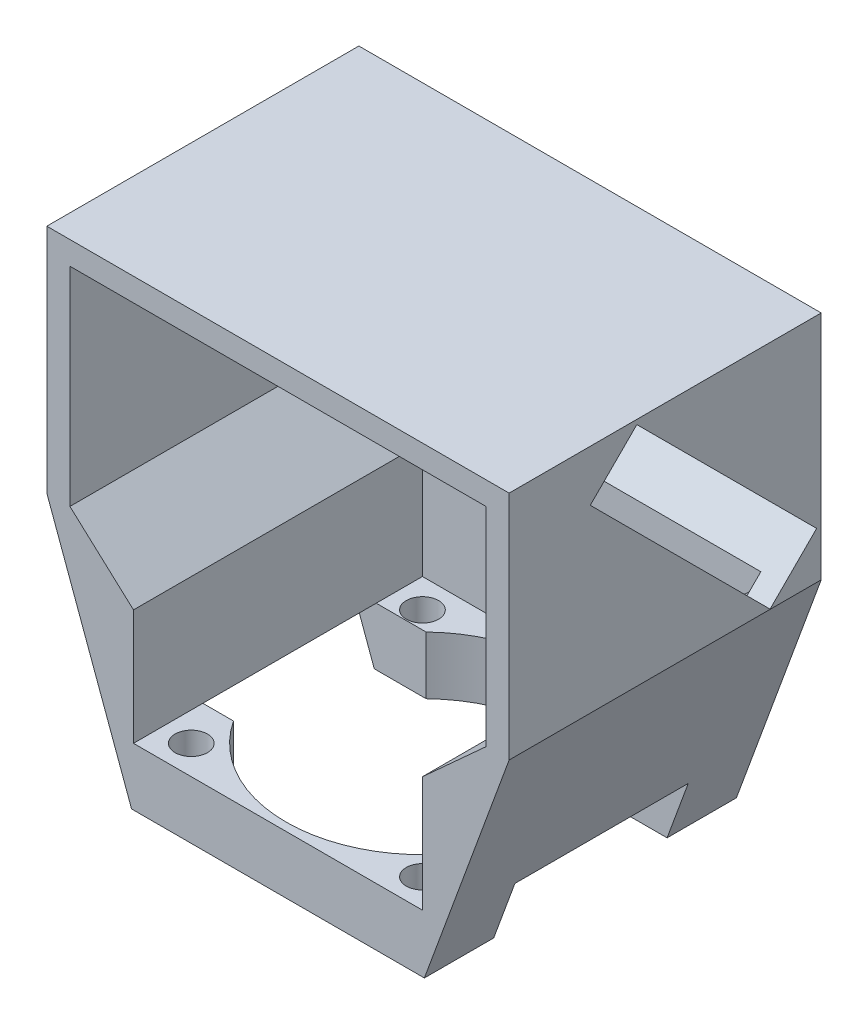
SolidWorks part; units mm, degrees
ref_plane "Front Plane" through (0, 0, 0) normal (1, 0, 0) x (0, 1, 0)
ref_plane "Top Plane" through (0, 0, 0) normal (0, 0, 1) x (0, 1, 0)
ref_plane "Right Plane" through (0, 0, 0) normal (0, 1, 0) x (-1, 0, 0)
sketch "Sketch2" plane through (0, 0, 0) normal (0, 0, 1) x (0, 1, 0)
  line L1 (-20, -20) -> (20, -20)
  line L2 (-20, -20) -> (-20, 20)
  line L3 (-20, 20) -> (20, 20)
  line L4 (20, -20) -> (20, 20)
  line L5 (-20, -20) -> (20, 20) construction
  line L6 (-20, 20) -> (20, -20) construction
  line L11 (-25, 12.5) -> (-15, -12.5) construction
  line L12 (-25, -12.5) -> (-15, 12.5) construction
  line L13 (-15, 12.5) -> (-5, 12.5)
  line L14 (-15, 12.5) -> (-15, -12.5)
  line L15 (-15, -12.5) -> (-5, -12.5)
  line L16 (-5, 12.5) -> (-5, -12.5)
  line L17 (20, 12.5) -> (5.2, 12.5)
  line L18 (20, 12.5) -> (20, -12.5)
  line L19 (20, -12.5) -> (5.2, -12.5)
  line L20 (5.2, 12.5) -> (5.2, -12.5)
  line L21 (-20, 12.5) -> (-15, 12.5)
  line L22 (-20, 12.5) -> (-20, -12.5)
  line L23 (-20, -12.5) -> (-15, -12.5)
  line L24 (-15, 12.5) -> (-15, -12.5)
  point P0 (0, 0)
  point P6 (-20, 0)
  dimension "D1" = 40
  dimension "D2" = 40
  dimension "D3" = 25
  dimension "D4" = 10
  dimension "D5" = 10
  dimension "D6" = 14.8
extrude "Boss-Extrude1" add sketch "Sketch2" along normal blind 25 contours L2 L23 L14 L21 region at (0, -17.5, 0)
extrude "Boss-Extrude2" add sketch "Sketch2<3>" against normal blind 2 contours L3 L4 L1 L2
sketch "Sketch2<3>" plane through (0, 0, 0) normal (0, 0, 1) x (0, 1, 0) same geometry as "Sketch2"
sketch "Sketch3" plane through (0, -20, 0) normal (0, -1, 0) x (1, 0, 0)
  line L1 (-12.5, 25) -> (12.5, 25)
  line L2 (-12.5, 25) -> (-12.5, 0)
  line L3 (-12.5, 0) -> (12.5, 0)
  line L4 (12.5, 25) -> (12.5, 0)
  circle A0 centre (0, 12.5) radius 11.8
  circle A1 centre (-10, 22.5) radius 1.4
  circle A2 centre (10, 22.5) radius 1.4
  circle A3 centre (10, 2.5) radius 1.4
  circle A4 centre (-10, 2.5) radius 1.4
  dimension "D1" = 4
extrude "Cut-Extrude1" cut sketch "Sketch3" against normal blind 21 and the other way through all contours A1 | A0 | A2 | A3 | A4 region at (0, -20, 12.5) region at (-10, -20, 22.5) region at (10, -20, 22.5) region at (10, -20, 2.5) region at (-10, -20, 2.5)
sketch "Sketch6" plane through (20, 0, 0) normal (1, 0, 0) x (0, 1, 0)
  line L0 (0, 0) -> (18, 18)
  line L1 (20, 0) -> (18, 0)
  line L2 (20, 0) -> (20, 25)
  line L3 (20, 25) -> (18, 25)
  line L4 (18, 0) -> (18, 25)
  line L5 (18, 0) -> (0, 0)
  line L6 (18, 0) -> (18, 18)
  line L7 (18, 18) -> (0, 18)
  line L8 (0, 0) -> (0, 18)
  dimension "D1" = 25
  dimension "D2" = 2
  dimension "D3" = 18
  dimension "D4" = 18
extrude "Boss-Extrude3" add sketch "Sketch6" against normal up to surface (40 mm away) contours L3 L4 L0 | L4 L3 L2 region at (20, 12, 6) region at (20, 19, 12.5) up to face at (-20, 0, -1)
sketch "Sketch7" plane through (0, 0, 0) normal (0, -0.7071, 0.7071) x (1, 0, 0)
  line L0 (20, 0) -> (20, 25.4558) construction
  line L1 (-20, 25.4558) -> (0, 25.4558)
  line L2 (-20, 25.4558) -> (-20, 12.7279)
  line L3 (-20, 12.7279) -> (0, 12.7279)
  line L4 (0, 25.4558) -> (0, 12.7279)
  line L5 (-18, 1.7279) -> (18, 1.7279)
  line L6 (-18, 1.7279) -> (-18, 23.7279)
  line L7 (-18, 23.7279) -> (18, 23.7279)
  line L8 (18, 1.7279) -> (18, 23.7279)
  line L9 (-18, 1.7279) -> (18, 23.7279) construction
  line L10 (-18, 23.7279) -> (18, 1.7279) construction
  line L11 (16, 4.7279) -> (20, 4.7279)
  line L12 (16, 4.7279) -> (16, 20.7279)
  line L13 (16, 20.7279) -> (20, 20.7279)
  line L14 (20, 4.7279) -> (20, 20.7279)
  line L15 (16, 4.7279) -> (20, 20.7279) construction
  line L16 (16, 20.7279) -> (20, 4.7279) construction
  point P9 (18, 12.7279)
  line M13 (20, 0) -> (20, 25.4558)
  dimension "D1" = 12.7279
  dimension "D2" = 22
  dimension "D3" = 36
  dimension "D4" = 16
extrude "Cut-Extrude2" cut sketch "Sketch7" against normal blind 4 contours L12 L13 L8 L7 L4 L3 L6 L5 L11 | L7 L6 L3 L4 | L13 L12 L11 L8 | L13 L8 L11 M13 region at (2.2028, 7.6298, 7.6298) region at (-9, 12.8891, 12.8891) region at (19, 9, 9) region at (17, 9, 9)
sketch "Sketch8" plane through (0, 0, 0) normal (0, 0, 1) x (1, 0, 0)
  line L0 (-18, 0) -> (-12.5, -15)
  line L1 (-12.5, -15) -> (-20, -15)
  line L2 (-12.5, -15) -> (-12.5, 0)
  line L3 (-12.5, 0) -> (-20, 0)
  line L4 (-20, -15) -> (-20, 0)
  line L5 (12.5, -15) -> (20, -15)
  line L6 (12.5, -15) -> (12.5, 0)
  line L7 (12.5, 0) -> (20, 0)
  line L8 (20, -15) -> (20, 0)
  line L9 (-20, 0) -> (-12.5, -20.4545)
  line L10 (-12.5, -15) -> (-12.5, -20.4545)
  line L11 (18, 0) -> (12.5, -15)
  line L12 (20, 0) -> (12.2526, -21.1292)
  line L13 (12.5, -15) -> (12.5, -20.4545)
  line M9 (20, 0) -> (-20, 0)
  line M11 (-20, -20) -> (-12.5, -20)
  line M12 (-12.5, -20) -> (-12.5, -15)
  line M14 (12.5, -15) -> (12.5, -20)
  line M15 (12.5, -20) -> (20, -20)
extrude "Boss-Extrude4" add sketch "Sketch8" along normal up to surface (25 mm away) contours L9 L1 L0 M9 | L1 L9 M11 M12 | L12 L11 L5 M9 | L12 L5 M14 M15 region at (-16.25, -7.5, 0) region at (-13.1709, -16.7949, 0) region at (16.25, -7.5, 0) region at (13.1709, -16.7949, 0) up to face at (0, -17.5, 25)
sketch "Sketch9" plane through (0, 0, 25) normal (0, 0, 1) x (1, 0, 0)
  line L1 (-20, 18) -> (-18, 18)
  line L2 (-20, 18) -> (-20, 0)
  line L3 (-20, 0) -> (-18, 0)
  line L4 (-18, 18) -> (-18, 0)
  line L5 (20, 18) -> (18, 18)
  line L6 (20, 18) -> (20, 0)
  line L7 (20, 0) -> (18, 0)
  line L8 (18, 18) -> (18, 0)
extrude "Boss-Extrude5" add sketch "Sketch9" against normal up to surface (7 mm away) up to face at (5.4286, 7.7143, 7.7143)
sketch "Sketch10" plane through (0, 0, 0) normal (0, 0, 1) x (1, 0, 0)
  line L0 (-20, 0) -> (-12.6667, -20)
  line L1 (-12.6667, -20) -> (-20, -20)
  line L2 (-20, -20) -> (-20, 0)
  line L3 (20, 0) -> (20, -20)
  line L4 (20, -20) -> (12.6667, -20)
  line L5 (12.6667, -20) -> (20, 0)
extrude "Cut-Extrude3" cut sketch "Sketch10" against normal blind 4
sketch "Sketch11" plane through (0, 0, 0) normal (0, 0, 1) x (1, 0, 0)
  line L0 (-12.5, -5) -> (-18, 0)
  line L1 (-12.5, -15) -> (12.5, -15)
  line L2 (-12.5, -15) -> (-12.5, -5)
  line L3 (-12.5, -5) -> (12.5, -5)
  line L4 (12.5, -15) -> (12.5, -5)
  line L5 (-20, 0) -> (-18, 0)
  line L6 (18, 0) -> (12.5, -5)
  line L7 (18, 0) -> (12.5, -15)
  line L8 (-18, 0) -> (-12.5, -15)
  line M6 (-18, 0) -> (-12.5, -15)
  line M8 (12.5, -15) -> (18, 0)
  dimension "D1" = 10
extrude "Boss-Extrude6" add sketch "Sketch11" along normal up to surface (25 mm away) contours L6 L4 M8 | L2 L0 M6 region at (-14.3333, -6.6667, 0) region at (14.3333, -6.6667, 0) up to face at (0, 1, 25)
sketch "Sketch12" plane through (20, 0, 0) normal (1, 0, 0) x (0, 1, 0)
  line L0 (6.1716, 0.5147) -> (17.4853, 11.8284)
  line L1 (6.1716, 0.5147) -> (1.9289, 4.7574)
  line L2 (17.4853, 11.8284) -> (13.2426, 16.0711)
  line L3 (1.9289, 4.7574) -> (13.2426, 16.0711)
  dimension "D1" = 6
extrude "Cut-Extrude4" cut sketch "Sketch12" against normal blind 4
sketch "Sketch13" plane through (18, 0, 0) normal (-1, 0, 0) x (0, -1, 0)
  line L0 (-19.6066, 13.9497) -> (-4.0503, -1.6066)
  line L1 (-19.6066, 13.9497) -> (-15.5761, 17.9803)
  line L2 (-4.0503, -1.6066) -> (-0.0197, 2.4239)
  line L3 (-15.5761, 17.9803) -> (-0.0197, 2.4239)
  dimension "D1" = 5.7
extrude "Cut-Extrude5" cut sketch "Sketch13" against normal blind 10
sketch "Sketch14" plane through (20, 0, 0) normal (1, 0, 0) x (0, 1, 0)
  line L0 (1.9289, 4.7574) -> (2.1411, 4.5452)
  line L1 (1.9289, 4.7574) -> (13.3484, 16.1769)
  line L2 (2.1411, 4.5452) -> (13.5606, 15.9647)
  line L3 (13.3484, 16.1769) -> (13.5606, 15.9647)
extrude "Boss-Extrude7" add sketch "Sketch14" against normal up to surface (2 mm away) up to face at (18, 8.3636, 12.3031)
sketch "Sketch15" plane through (20, 0, 0) normal (1, 0, 0) x (0, 1, 0)
  line L0 (-20, 25) -> (-20, -2) construction
  line L1 (-25, 4) -> (-15, 4)
  line L2 (-25, 4) -> (-25, 19)
  line L3 (-25, 19) -> (-15, 19)
  line L4 (-15, 4) -> (-15, 19)
  line L5 (-25, 4) -> (-15, 19) construction
  line L6 (-25, 19) -> (-15, 4) construction
  point P0 (-20, 11.5)
  dimension "D1" = 10
  dimension "D2" = 15
extrude "Cut-Extrude6" cut sketch "Sketch15" against normal blind 37
